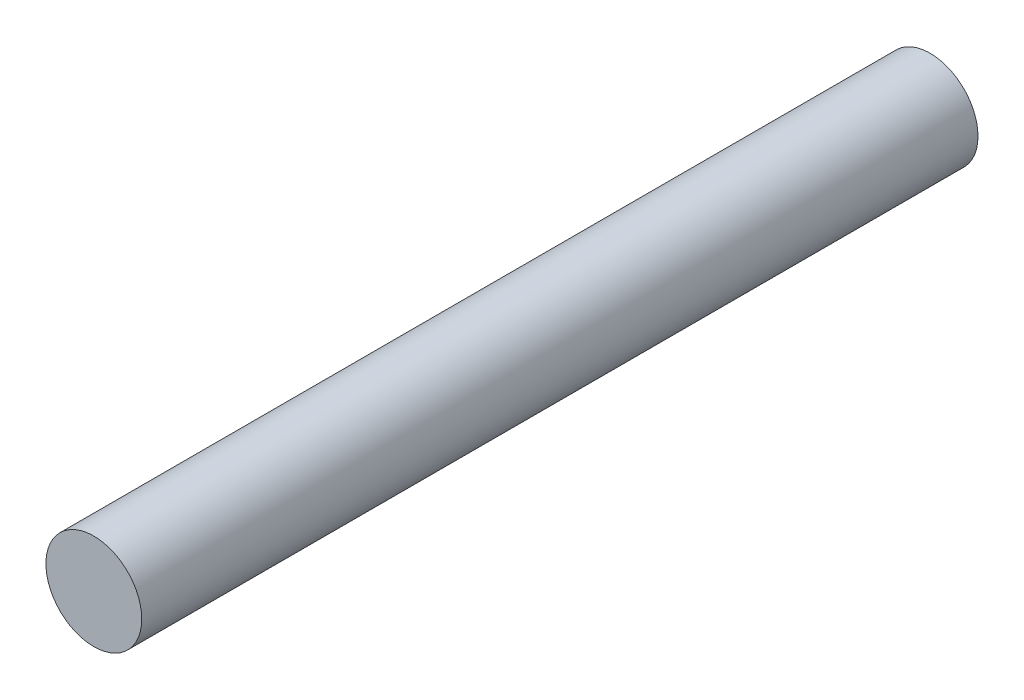
SolidWorks part; units mm, degrees
ref_plane "Alzado" through (0, 0, 0) normal (0, 0, 1) x (1, 0, 0)
ref_plane "Planta" through (0, 0, 0) normal (0, 1, 0) x (1, 0, 0)
ref_plane "Vista lateral" through (0, 0, 0) normal (1, 0, 0) x (0, 0, -1)
sketch "Croquis1" plane through (0, 0, 0) normal (0, 0, 1) x (1, 0, 0)
  circle A0 centre (0, 0) radius 2.75
  dimension "D1" = 5.5
extrude "Saliente-Extruir1" add sketch "Croquis1" along normal blind 48
